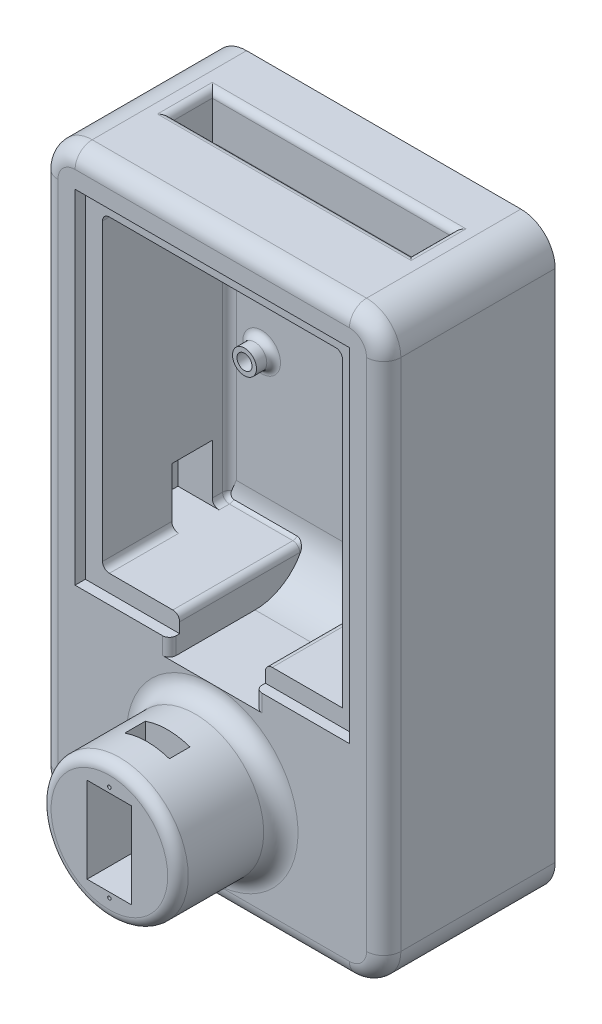
SolidWorks part; units mm, degrees
note: The reader was unsure of these and kept them because the rebuilt part matched: shared geometry of "Skica2<2>".
ref_plane "Přední rovina" through (0, 0, 0) normal (0, 0, 1) x (1, 0, 0)
ref_plane "Horní rovina" through (0, 0, 0) normal (0, 1, 0) x (1, 0, 0)
ref_plane "Pravá rovina" through (0, 0, 0) normal (1, 0, 0) x (0, 0, -1)
sketch "Skica1" plane through (0, 0, 0) normal (0, 0, 1) x (1, 0, 0)
  line L11 (0, 0) -> (100, 0)
  line L12 (0, 0) -> (0, 170)
  line L13 (0, 170) -> (100, 170)
  line L14 (100, 0) -> (100, 170)
  dimension "D1" = 100
  dimension "D2" = 170
extrude "Přidat vysunutím3" add sketch "Skica1" along normal blind 50
fillet "Zaoblit1" radius 10 4 edges at (100, 0, 25) (100, 170, 25) (0, 170, 25) (0, 0, 25)
sketch "Skica2" plane through (0, 0, 50) normal (0, 0, 1) x (1, 0, 0)
  line L0 (0, 160) -> (0, 10) construction
  line L1 (90, 170) -> (10, 170) construction
  circle A0 centre (50, 30) radius 20
  dimension "D1" = 40
  dimension "D2" = 50
  dimension "D3" = 140
extrude "Přidat vysunutím4" add sketch "Skica2" along normal blind 30
fillet "Zaoblit2" radius 5 1 edges at (30, 30, 50)
fillet "Zaoblit3" radius 3 1 edges at (70, 30, 80)
sketch "Skica4" plane through (0, 0, 50) normal (0, 0, 1) x (1, 0, 0)
  line L0 (0, 160) -> (0, 10) construction
  line L1 (15, 155) -> (85, 155)
  line L2 (15, 155) -> (15, 65)
  line L3 (15, 65) -> (85, 65)
  line L4 (85, 155) -> (85, 65)
  line L5 (90, 170) -> (10, 170) construction
  line L6 (100, 10) -> (100, 160) construction
  circle A0 centre (50, 30) radius 25 construction
  dimension "D1" = 15
  dimension "D2" = 15
  dimension "D3" = 15
  dimension "D4" = 35
fillet "Zaoblit5" radius 5 8 edges at (2.9289, 2.9289, 50) (0, 85, 50) (2.9289, 167.0711, 50) (50, 170, 50) (97.0711, 167.0711, 50) (100, 85, 50) (97.0711, 2.9289, 50) (50, 0, 50)
sketch "Skica9" plane through (0, 0, 80) normal (0, 0, 1) x (1, 0, 0)
  line L0 (43.5, 42.5) -> (56.5, 17.5)
  line L1 (43.5, 42.5) -> (56.5, 42.5)
  line L2 (43.5, 42.5) -> (43.5, 17.5)
  line L3 (43.5, 17.5) -> (56.5, 17.5)
  line L4 (56.5, 42.5) -> (56.5, 17.5)
  line L5 (56.5, 42.5) -> (43.5, 17.5)
  line L6 (50, 47) -> (50, 13)
  line L7 (33, 30) -> (67, 30)
  circle A0 centre (50, 30) radius 17 construction
  point P9 (50, 30)
  point P12 (50, 30)
  dimension "D1" = 25
  dimension "D2" = 13
extrude "Odebrat vysunutím3" cut sketch "Skica9" against normal blind 20 contours L2 L7 L0 | L6 L1 L0 | L1 L6 L5 | L5 L7 L4 | L7 L0 L4 | L0 L6 L3 | L6 L5 L3 | L7 L2 L5
sketch "Skica10" plane through (0, 42.5, 0) normal (0, -1, 0) x (-1, 0, 0)
  line L1 (-43.5, -63) -> (-56.5, -63)
  line L2 (-43.5, -63) -> (-43.5, -69)
  line L3 (-43.5, -69) -> (-56.5, -69)
  line L4 (-56.5, -63) -> (-56.5, -69)
  line L5 (-56.5, -60) -> (-56.5, -80) construction
  line L7 (-67, -80) -> (-33, -80) construction
  dimension "D1" = 6
  dimension "D2" = 13
  dimension "D3" = 0
  dimension "D4" = 11
extrude "Odebrat vysunutím4" cut sketch "Skica10" against normal through all
extrude "Odebrat vysunutím5" cut sketch "Skica4" against normal blind 40
sketch "Skica12" plane through (0, 0, 50) normal (0, 0, 1) x (1, 0, 0)
  line L0 (15, 65) -> (85, 65) construction
  line L1 (37.5, 65) -> (62.5, 65)
  line L2 (37.5, 65) -> (37.5, 55)
  line L3 (37.5, 55) -> (62.5, 55)
  line L4 (62.5, 65) -> (62.5, 55)
  line L6 (85, 155) -> (15, 155) construction
  point P6 (50, 155)
  point P9 (50, 65)
  dimension "D1" = 25
  dimension "D2" = 10
extrude "Odebrat vysunutím6" cut sketch "Skica12" against normal blind 40
fillet "Zaoblit7" radius 2 1 edges at (37.5, 60, 50)
fillet "Zaoblit8" radius 2 1 edges at (62.5, 60, 50)
sketch "Skica13" plane through (0, 0, 50) normal (0, 0, 1) x (1, 0, 0)
  line L0 (10, 160) -> (10, 60)
  line L1 (10, 60) -> (90, 60)
  line L2 (90, 60) -> (90, 160)
  line L3 (90, 160) -> (10, 160)
  line L4 (85, 155) -> (15, 155) construction
  line L5 (15, 155) -> (15, 65) construction
  line L6 (15, 65) -> (35.5, 65) construction
  line L7 (85, 65) -> (85, 155) construction
  dimension "D1" = 5
  dimension "D2" = 5
  dimension "D3" = 5
  dimension "D4" = 5
extrude "Odebrat vysunutím7" cut sketch "Skica13" against normal blind 3
sketch "Skica14" plane through (0, 155, 0) normal (0, -1, 0) x (-1, 0, 0)
  line L0 (-85, -10) -> (-15, -10) construction
  line L1 (-15, -10) -> (-85, -10)
  line L2 (-15, -10) -> (-15, -30)
  line L3 (-15, -30) -> (-85, -30)
  line L4 (-85, -10) -> (-85, -30)
  line L5 (-85, -10) -> (-85, -47) construction
  line L6 (-15, -10) -> (-15, -47) construction
  dimension "D1" = 20
sketch "Skica15" plane through (0, 0, 10) normal (0, 0, 1) x (1, 0, 0)
  line L1 (24.4, 142.8) -> (75.6, 142.8)
  line L2 (15, 155) -> (85, 155) construction
  line L3 (10, 170) -> (90, 170) construction
  circle A0 centre (24.4, 142.8) radius 3.5
  circle A1 centre (75.6, 142.8) radius 3.5
  circle A2 centre (24.4, 106.1) radius 3.5
  circle A3 centre (75.6, 106.1) radius 3.5
  point P6 (50, 155)
  point P7 (50, 142.8)
  dimension "D1" = 7
  dimension "D2" = 7
  dimension "D3" = 51.2
  dimension "D5" = 7
  dimension "D6" = 7
  dimension "D4" = 23.7
  dimension "D7" = 36.7
extrude "Přidat vysunutím5" add sketch "Skica15" along normal blind 5
sketch "Skica19" plane through (0, 0, 15) normal (0, 0, 1) x (1, 0, 0)
  circle A0 centre (24.4, 142.8) radius 2.2
  circle A1 centre (24.4, 142.8) radius 3.5 construction
  circle A2 centre (75.6, 142.8) radius 2.2
  circle A3 centre (75.6, 106.1) radius 2.2
  circle A4 centre (24.4, 106.1) radius 2.2
  circle A5 centre (24.4, 106.1) radius 3.5 construction
  dimension "D1" = 4.4
  dimension "D2" = 4.4
  dimension "D3" = 4.4
  dimension "D4" = 4.4
extrude "Odebrat vysunutím8" cut sketch "Skica19" against normal blind 8
fillet "Zaoblit9" radius 2 4 edges at (79.1, 106.1, 10) (27.9, 106.1, 10) (27.9, 142.8, 10) (79.1, 142.8, 10)
sketch "Skica20" plane through (0, 155, 0) normal (0, -1, 0) x (1, 0, 0)
  line L0 (15, 10) -> (85, 10) construction
  line L1 (15, 15) -> (85, 15)
  line L2 (15, 15) -> (15, 27)
  line L3 (15, 27) -> (85, 27)
  line L4 (85, 15) -> (85, 27)
  line L6 (85, 10) -> (85, 47) construction
  line L7 (15, 10) -> (15, 47) construction
  dimension "D1" = 5
  dimension "D2" = 12
extrude "Odebrat vysunutím9" cut sketch "Skica20" against normal up to next
sketch "Skica21" plane through (15, 0, 0) normal (1, 0, 0) x (0, 0, -1)
  line L0 (-10, 65) -> (-47, 65) construction
  line L1 (-15, 65) -> (-26.8, 65)
  line L2 (-15, 65) -> (-15, 81.6)
  line L3 (-15, 81.6) -> (-26.8, 81.6)
  line L4 (-26.8, 65) -> (-26.8, 81.6)
  line L5 (-10, 155) -> (-10, 65) construction
  dimension "D1" = 16.6
  dimension "D2" = 5
  dimension "D3" = 11.8
extrude "Odebrat vysunutím10" cut sketch "Skica21" against normal blind 10
sketch "Skica22" plane through (5, 0, 0) normal (1, 0, 0) x (0, 0, -1)
  line L0 (-15, 65) -> (-15, 81.6) construction
  line L1 (-25.8, 69.3) -> (-22.8, 69.3)
  line L2 (-25.8, 69.3) -> (-25.8, 77.3)
  line L3 (-25.8, 77.3) -> (-22.8, 77.3)
  line L4 (-22.8, 69.3) -> (-22.8, 77.3)
  line L6 (-26.8, 81.6) -> (-26.8, 65) construction
  point P6 (-15, 73.3)
  point P7 (-22.8, 73.3)
  dimension "D1" = 3
  dimension "D2" = 8
  dimension "D3" = 1
extrude "Odebrat vysunutím11" cut sketch "Skica22" against normal through all
fillet "Zaoblit10" radius 2 1 edges at (85, 110, 10)
fillet "Zaoblit11" radius 2 2 edges at (15, 110, 10) (26.25, 65, 10)
fillet "Zaoblit12" radius 2 1 edges at (15, 65, 36.9)
fillet "Zaoblit13" radius 2 2 edges at (15, 65, 13.5) (15.5858, 65.5858, 10.5858)
fillet "Zaoblit14" radius 2 1 edges at (15, 155, 37)
fillet "Zaoblit15" radius 2 1 edges at (85, 155, 37)
fillet "Zaoblit16" radius 2 5 edges at (85, 155, 13.5) (84.4142, 155, 10.5858) (15, 155, 13.5) (15.5858, 155, 10.5858) (50, 155, 10)
fillet "Zaoblit17" radius 2 3 edges at (15.5858, 154.4142, 15) (84.4142, 154.4142, 15) (50, 155, 15)
fillet "Zaoblit19" radius 2 2 edges at (37.5, 65, 29.5) (37.5, 65.5858, 10.5858)
fillet "Zaoblit20" radius 2 3 edges at (84.4142, 154.4142, 27) (15.5858, 154.4142, 27) (50, 155, 27)
fillet "Zaoblit21" radius 2 1 edges at (50, 170, 27)
fillet "Zaoblit22" radius 2 1 edges at (50, 170, 15)
fillet "Zaoblit23" radius 2 1 edges at (15, 170, 21)
fillet "Zaoblit24" radius 2 1 edges at (85, 170, 21)
fillet "Zaoblit25" radius 2 1 edges at (62.5, 65, 28.5)
sketch "Skica25" plane through (0, 0, 80) normal (0, 0, 1) x (1, 0, 0)
  line L0 (43.5, 42.5) -> (56.5, 42.5) construction
  line L1 (43.5, 42.5) -> (43.5, 17.5) construction
  line L2 (56.5, 42.5) -> (56.5, 17.5) construction
  circle A0 centre (50, 44) radius 0.5
  circle A1 centre (50, 16) radius 0.5
  point P7 (50, 42.5)
  point P11 (43.5, 30)
  point P14 (56.5, 30)
  dimension "D1" = 1
  dimension "D2" = 1
  dimension "D3" = 14
  dimension "D4" = 14
extrude "Odebrat vysunutím13" cut sketch "Skica25" against normal blind 8
fillet "Zaoblit29" radius 15 1 edges at (50, 55, 10)
extrude "Odebrat vysunutím14" cut sketch "Skica2<2>" against normal offset from surface (50 mm away) 1.2 from offset 1.2
sketch "Skica2<2>" plane through (0, 0, 50) normal (0, 0, 1) x (1, 0, 0) same geometry as "Skica2"
sketch "Skica27" plane through (0, 0, 50) normal (0, 0, 1) x (1, 0, 0)
  circle A0 centre (50, 30) radius 19.6
  circle A2 centre (50, 30) radius 20 construction
  dimension "D1" = 0.4
extrude "Přidat vysunutím8" add sketch "Skica27" against normal up to surface (50 mm away) up to face at (50, 85, 0)
sketch "Skica28" plane through (0, 0, 0) normal (0, 0, -1) x (-1, 0, 0)
  line L0 (0, 160) -> (0, 10) construction
  line L1 (-16, 30.4034) -> (-27, 24.0526)
  line L2 (-27, 24.0526) -> (-27, 11.3509)
  line L3 (-27, 11.3509) -> (-16, 5)
  line L4 (-16, 5) -> (-5, 11.3509)
  line L5 (-5, 11.3509) -> (-5, 24.0526)
  line L6 (-5, 24.0526) -> (-16, 30.4034)
  line L7 (-95, 24.0526) -> (-84, 30.4034)
  line L8 (-95, 11.3509) -> (-95, 24.0526)
  line L9 (-10, 0) -> (-90, 0) construction
  line L10 (-50, 0) -> (-50, 170) construction
  line L11 (-90, 170) -> (-10, 170) construction
  line L12 (0, 32) -> (-100, 32) construction
  line L13 (-100, 10) -> (-100, 160) construction
  line L14 (-84, 5) -> (-95, 11.3509)
  line L15 (-73, 11.3509) -> (-84, 5)
  line L16 (-73, 24.0526) -> (-73, 11.3509)
  line L17 (-84, 30.4034) -> (-73, 24.0526)
  line L18 (-5, 39.9474) -> (-16, 33.5966)
  line L19 (-5, 52.6491) -> (-5, 39.9474)
  line L20 (-16, 59) -> (-5, 52.6491)
  line L21 (-27, 52.6491) -> (-16, 59)
  line L22 (-27, 39.9474) -> (-27, 52.6491)
  line L23 (-16, 33.5966) -> (-27, 39.9474)
  line L24 (-95, 52.6491) -> (-95, 39.9474)
  line L25 (-84, 59) -> (-95, 52.6491)
  line L26 (-73, 52.6491) -> (-84, 59)
  line L27 (-73, 39.9474) -> (-73, 52.6491)
  line L28 (-84, 33.5966) -> (-73, 39.9474)
  line L29 (-95, 39.9474) -> (-84, 33.5966)
  circle A0 centre (-16, 17.7017) radius 11 construction
  dimension "D1" = 22
  dimension "D2" = 5
  dimension "D3" = 5
  dimension "D4" = 32
extrude "Odebrat vysunutím15" cut sketch "Skica28" against normal blind 34 from offset 1.2 contours L24 L29 L28 L27 L26 L25 | L18 L23 L22 L21 L20 L19 | L1 L2 L3 L4 L5 L6 | L7 L17 L16 L15 L14 L8 offset against normal yes
sketch "Skica29" plane through (0, 0, 0) normal (0, 0, -1) x (-1, 0, 0)
  line L0 (-10, 0) -> (-90, 0) construction
  line L1 (-39, 36.3509) -> (-50, 42.7017)
  line L2 (-50, 42.7017) -> (-61, 36.3509)
  line L3 (-61, 36.3509) -> (-61, 23.6491)
  line L4 (-61, 23.6491) -> (-50, 17.2983)
  line L5 (-50, 17.2983) -> (-39, 23.6491)
  line L6 (-39, 23.6491) -> (-39, 36.3509)
  circle A0 centre (-50, 30) radius 11 construction
  point P1 (0, 0)
  point P9 (0, 0)
  point P12 (-50, 0)
  point P13 (0, 0)
  point P17 (0, 0)
  dimension "D1" = 22
  dimension "D2" = 30
extrude "Odebrat vysunutím16" cut sketch "Skica29" against normal blind 11.5 from offset 23.7 offset against normal yes
sketch "Skica30" plane through (0, 0, 47) normal (0, 0, 1) x (1, 0, 0)
  line L0 (90, 160) -> (10, 160) construction
  line L1 (10, 160) -> (10, 60) construction
  line L2 (50, 160) -> (50, 55) construction
  line L3 (90, 160) -> (10, 160) construction
  line L4 (62.5, 55) -> (37.5, 55) construction
  line L5 (10, 110) -> (90, 110) construction
  line L6 (10, 160) -> (10, 60) construction
  line L7 (90, 60) -> (90, 160) construction
  circle A0 centre (13, 157) radius 3
  circle A1 centre (87, 157) radius 3
  circle A2 centre (87, 63) radius 3
  circle A3 centre (13, 63) radius 3
  dimension "D1" = 6
extrude "Odebrat vysunutím17" cut sketch "Skica30" against normal blind 2.6 from offset 0.2 offset against normal yes
